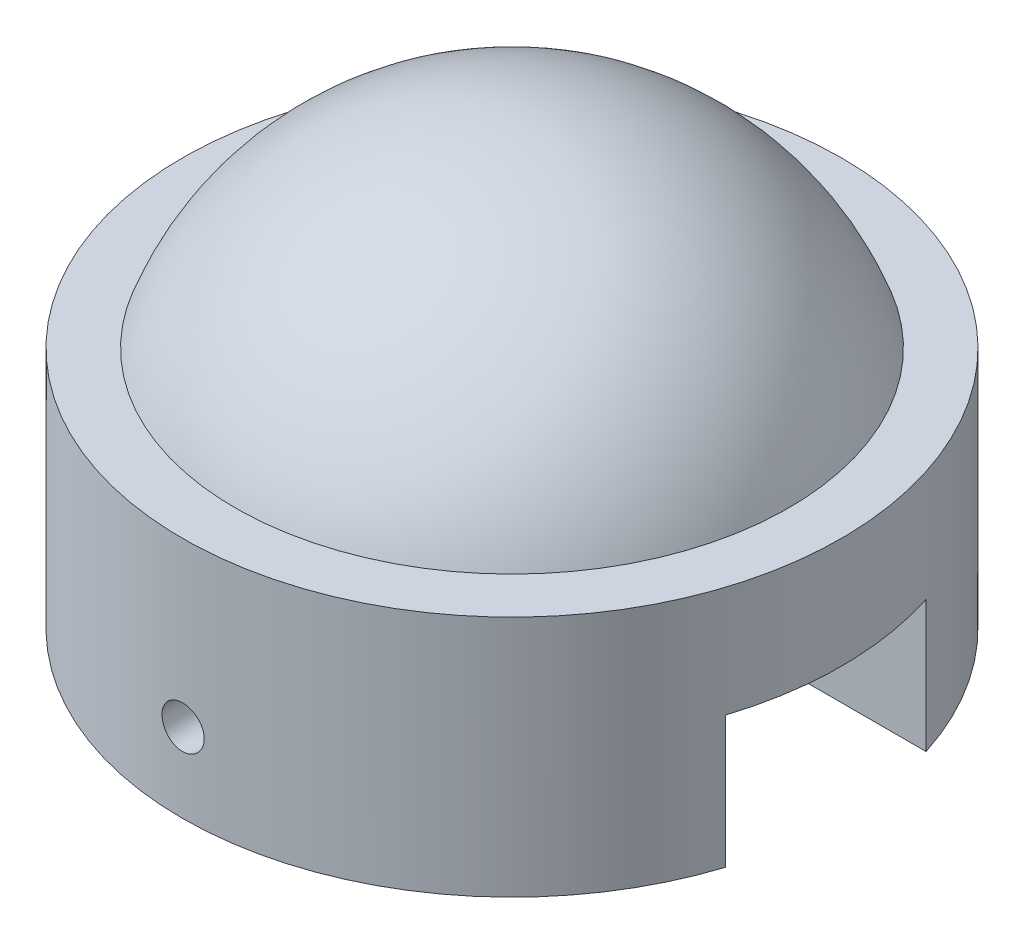
SolidWorks part; units mm, degrees
ref_plane "Front Plane" through (0, 0, 0) normal (0, 0, 1) x (1, 0, 0)
ref_plane "Top Plane" through (0, 0, 0) normal (0, 1, 0) x (1, 0, 0)
ref_plane "Right Plane" through (0, 0, 0) normal (1, 0, 0) x (0, 0, -1)
sketch "Sketch1" plane through (0, 0, 0) normal (0, 0, 1) x (1, 0, 0)
  line L0 (0, 0) -> (0, 12) construction
  line L1 (0, 8.3) -> (0, 5.6)
  line L2 (-6.25, 0) -> (-6.25, 4.6)
  line L3 (-3.9, 0) -> (-3.9, 4.2)
  line L5 (-3.9, 0) -> (-6.25, 0)
  line L6 (0, 5.6) -> (2.7861, 5.6) construction
  line L7 (-6.25, 4.6) -> (-5.25, 4.6)
  arc A2 (0, 5.6) -> (-3.9, 4.2) centre (0, -0.5321) ccw
  arc A4 (0, 8.3) -> (-5.25, 4.6) centre (0, 2.7253) ccw
  point P10 (-5.256, 4.6)
  dimension "D1" = 7.8
  dimension "D2" = 12.5
  dimension "D3" = 4.6
  dimension "D4" = 5.6
  dimension "D5" = 8.3
  dimension "D6" = 4.2
  dimension "D7" = 1
revolve "Revolve1" add sketch "Sketch1" angle 360 about L0
sketch "Sketch2" plane through (0, 0, 0) normal (1, 0, 0) x (0, 0, -1)
  line L0 (0, 0) -> (0, 5.2513) construction
  line L1 (1.9, 0) -> (-1.9, 0)
  line L2 (1.9, 0) -> (1.9, 2.5)
  line L3 (1.9, 2.5) -> (-1.9, 2.5)
  line L4 (-1.9, 0) -> (-1.9, 2.5)
  dimension "D1" = 3.8
  dimension "D2" = 2.5
extrude "Cut-Extrude1" cut sketch "Sketch2" against normal through all and the other way blind 10
sketch "Sketch3" plane through (0, 0, 0) normal (0, 0, 1) x (1, 0, 0)
  circle A0 centre (0, 1.5) radius 0.4
  point P2 (0, 0)
  point P4 (0, 0)
  point P5 (0, 0)
  dimension "D1" = 0.8
  dimension "D2" = 1.5
extrude "Cut-Extrude2" cut sketch "Sketch3" against normal through all and the other way through all
